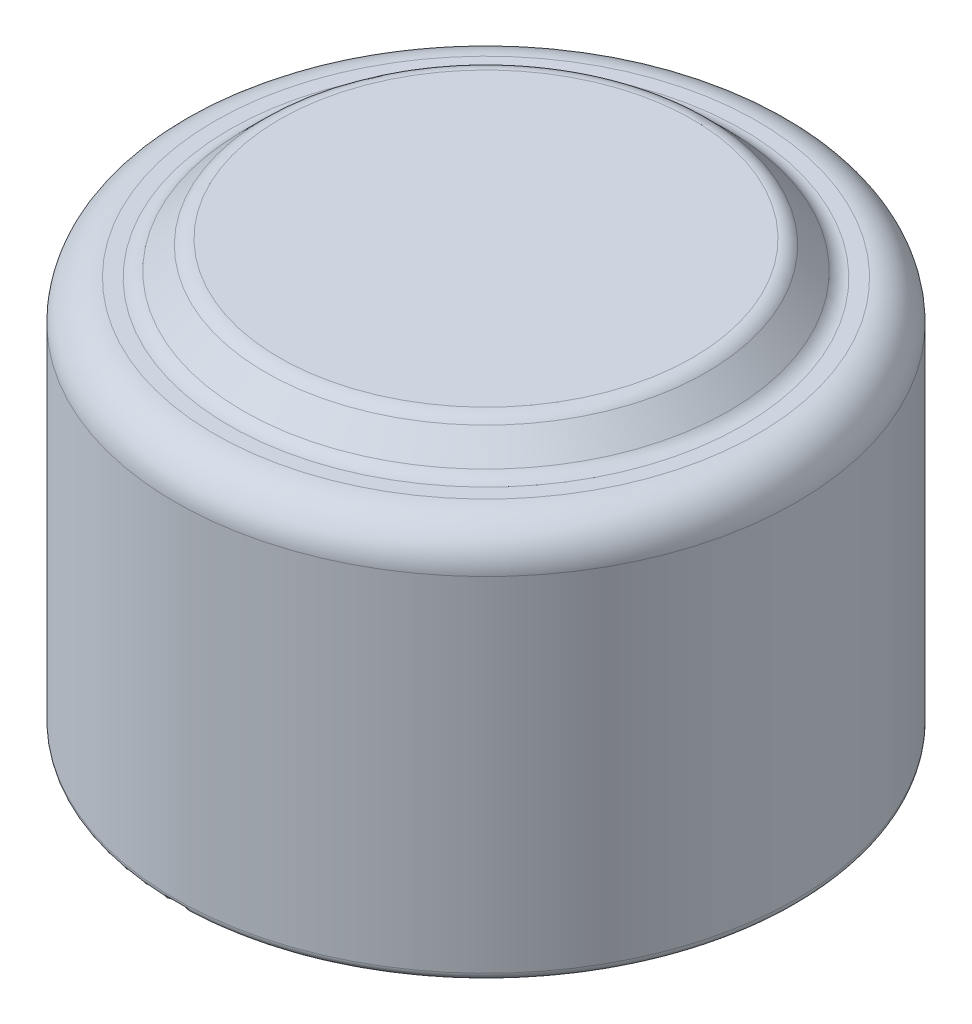
SolidWorks part; units mm, degrees
ref_plane "Front Plane" through (0, 0, 0) normal (0, 0, 1) x (1, 0, 0)
ref_plane "Top Plane" through (0, 0, 0) normal (0, 1, 0) x (1, 0, 0)
ref_plane "Right Plane" through (0, 0, 0) normal (1, 0, 0) x (0, 0, -1)
sketch "Sketch1" plane through (0, 0, 0) normal (0, 0, 1) x (1, 0, 0)
  line L0 (0, 0) -> (-3.85, 0)
  line L1 (-3.95, 0.1) -> (-3.95, 4.47)
  line L2 (-2.6264, 5.4) -> (0, 5.4)
  line L3 (0, 5.4) -> (0, 0)
  line L4 (-2.8032, 5.3268) -> (-3.0868, 5.0432)
  line L7 (-3.45, 4.97) -> (-3.2636, 4.97)
  arc A0 (-3.95, 4.47) -> (-3.45, 4.97) centre (-3.45, 4.47) cw
  arc A1 (-2.6264, 5.4) -> (-2.8032, 5.3268) centre (-2.6264, 5.15) ccw
  arc A2 (-3.2636, 4.97) -> (-3.0868, 5.0432) centre (-3.2636, 5.22) ccw
  arc A3 (-3.85, 0) -> (-3.95, 0.1) centre (-3.85, 0.1) cw
  point P9 (-3.95, 4.97)
  point P14 (-2.73, 5.4)
  point P17 (-3.95, 0)
  point P18 (-3.16, 4.97)
  dimension "D6" = 0.5
  dimension "D7" = 0.25
  dimension "D8" = 0.1
  dimension "D1" = 3.95
  dimension "D2" = 5.4
  dimension "D3" = 3.16
  dimension "D4" = 4.97
  dimension "D5" = 45
revolve "Revolve1" add sketch "Sketch1" angle 360 about L3
sketch "Sketch2" plane through (0, 0, 0) normal (0, -1, 0) x (1, 0, 0)
  line L0 (0.25, -0.25) -> (0.25, -1.5)
  line L1 (-0.25, 1.5) -> (0.25, 1.5)
  line L2 (-0.25, 1.5) -> (-0.25, 0.25)
  line L3 (-0.25, -1.5) -> (0.25, -1.5)
  line L4 (0.25, 1.5) -> (0.25, 0.25)
  line L5 (-1.5, 0.25) -> (-0.25, 0.25)
  line L6 (-1.5, 0.25) -> (-1.5, -0.25)
  line L7 (-1.5, -0.25) -> (-0.25, -0.25)
  line L8 (1.5, 0.25) -> (1.5, -0.25)
  line L9 (-0.25, -0.25) -> (-0.25, -1.5)
  line L10 (0.25, 0.25) -> (1.5, 0.25)
  line L11 (0.25, -0.25) -> (1.5, -0.25)
  circle A0 centre (0, 0) radius 2.5 construction
  text T0 "                    SR48" font "Century Gothic" height 1
  dimension "D1" = 5
  dimension "D2" = 0.5
  dimension "D3" = 0.5
  dimension "D4" = 0.25
  dimension "D5" = 0.25
  dimension "D6" = 3
  dimension "D7" = 3
  dimension "D8" = 1.5
  dimension "D9" = 1.5
wrap "Wrap1" sketch "Sketch2" wrap type scribe source sketch "Sketch2" face at (-3.85, 0, 0)
